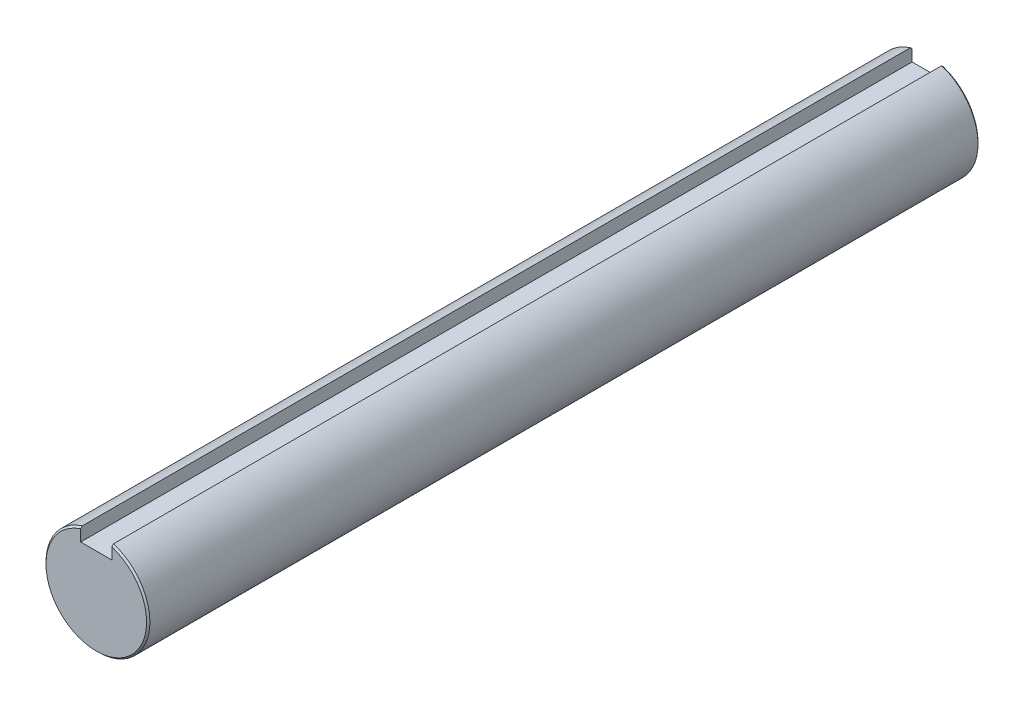
SolidWorks part; units mm, degrees
material "AISI 1045 Steel, cold drawn"
ref_plane "Front Plane" through (0, 0, 0) normal (0, 0, 1) x (1, 0, 0)
ref_plane "Top Plane" through (0, 0, 0) normal (0, 1, 0) x (1, 0, 0)
ref_plane "Right Plane" through (0, 0, 0) normal (1, 0, 0) x (0, 0, -1)
sketch "Sketch1" plane through (0, 0, 0) normal (0, 0, 1) x (1, 0, 0)
  line L1 (-2.3813, 5.5562) -> (2.3813, 5.5562)
  line L2 (-2.3813, 5.5562) -> (-2.3813, 10.3187)
  line L3 (-2.3813, 10.3187) -> (2.3813, 10.3187)
  line L4 (2.3813, 5.5562) -> (2.3813, 10.3187)
  line L5 (-2.3813, 5.5562) -> (2.3813, 10.3187) construction
  line L6 (-2.3813, 10.3187) -> (2.3813, 5.5562) construction
  circle A0 centre (0, 0) radius 7.9375
  point P3 (0, 7.9375)
  dimension "D1" = 15.875
  dimension "D2" = 4.7625
  dimension "D3" = 4.7625
extrude "Boss-Extrude1" add sketch "Sketch1" along normal blind 127 contours L2 A0 L4 L1 region at (0, -0.3848, 0)
chamfer "Chamfer1" distance 0.254 angle 45 2 edges at (0, -7.9375, 0) (0, -7.9375, 127)
ref_axis "Axis1" through (0, 0, 126.746) along (0, 0, -1)
